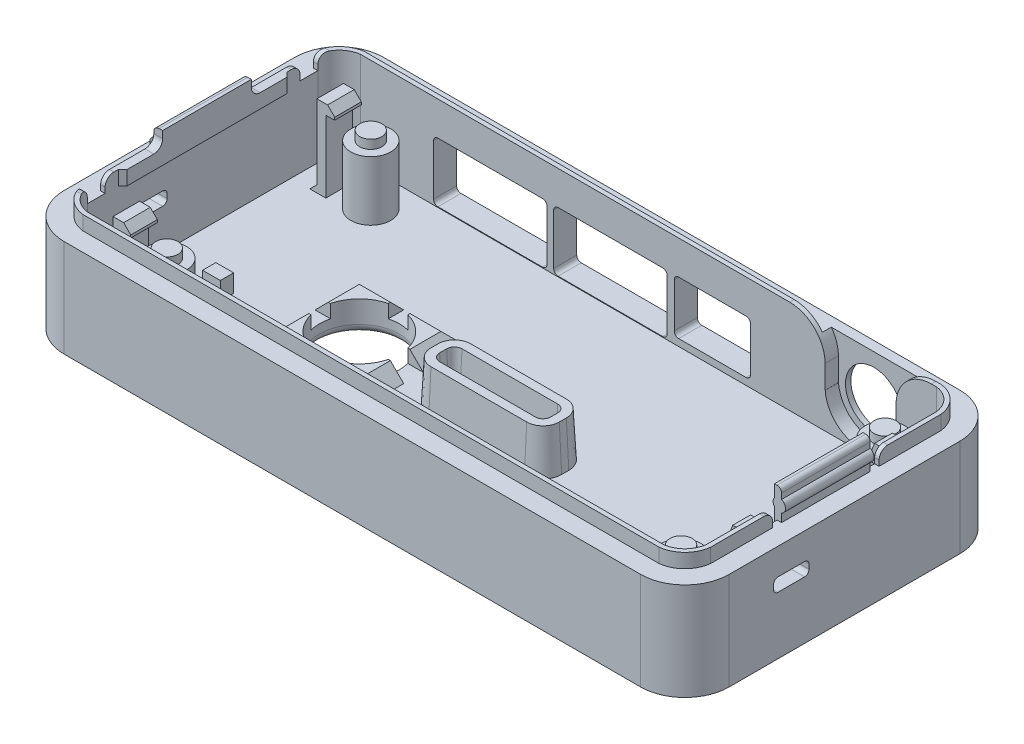
SolidWorks part; units mm, degrees
ref_plane "前视基准面" through (0, 0, 0) normal (0, 0, 1) x (1, 0, 0)
ref_plane "上视基准面" through (0, 0, 0) normal (0, 1, 0) x (1, 0, 0)
ref_plane "右视基准面" through (0, 0, 0) normal (1, 0, 0) x (0, 0, -1)
sketch "zero" plane through (0, 0, 0) normal (0, 1, 0) x (1, 0, 0)
  line L1 (-29.5, 15) -> (29.5, 15)
  line L2 (-32.5, 12) -> (-32.5, -12)
  line L3 (-29.5, -15) -> (29.5, -15)
  line L4 (32.5, 12) -> (32.5, -12)
  line L5 (-32.5, 15) -> (32.5, -15) construction
  line L6 (-32.5, -15) -> (32.5, 15) construction
  line L7 (-25.7, -15) -> (-14.5, -15)
  line L8 (-25.7, -15) -> (-25.7, -9.6569)
  line L9 (-25.7, -9.6569) -> (-14.5, -9.6569)
  line L10 (-14.5, -15) -> (-14.5, -9.6569)
  line L11 (5.2, -15) -> (12.7, -15)
  line L12 (5.2, -15) -> (5.2, -11)
  line L13 (5.2, -11) -> (12.7, -11)
  line L14 (12.7, -15) -> (12.7, -11)
  line L15 (17.8, -15) -> (25.3, -15)
  line L16 (17.8, -15) -> (17.8, -11)
  line L17 (17.8, -11) -> (25.3, -11)
  line L18 (25.3, -15) -> (25.3, -11)
  line L19 (-32.5, 7.7) -> (-19.5, 7.7)
  line L20 (-32.5, 7.7) -> (-32.5, -4.3)
  line L21 (-32.5, -4.3) -> (-19.5, -4.3)
  line L22 (-19.5, 7.7) -> (-19.5, -4.3)
  line L23 (-25.5, 14) -> (25.5, 14)
  line L24 (-25.5, 14) -> (-25.5, 8.8)
  line L25 (-25.5, 8.8) -> (25.5, 8.8)
  line L26 (25.5, 14) -> (25.5, 8.8)
  line L27 (-19.5, 7.2329) -> (-35.5, 7.2329)
  line L28 (-19.5, 7.2329) -> (-19.5, -3.7671)
  line L29 (-19.5, -3.7671) -> (-35.5, -3.7671)
  line L30 (-35.5, 7.2329) -> (-35.5, -3.7671)
  arc A0 (29.5, -15) -> (32.5, -12) centre (29.5, -12) ccw
  arc A1 (29.5, 15) -> (32.5, 12) centre (29.5, 12) cw
  arc A2 (-32.5, -12) -> (-29.5, -15) centre (-29.5, -12) ccw
  arc A3 (-29.5, 15) -> (-32.5, 12) centre (-29.5, 12) ccw
  circle A4 centre (-29, 11.4) radius 3
  circle A5 centre (-29, -11.5) radius 3
  circle A6 centre (29, 11.4) radius 3
  circle A7 centre (29, -11.5) radius 3
  circle A8 centre (-29, 11.4) radius 1.375
  circle A9 centre (-29, -11.5) radius 1.375
  circle A10 centre (29, -11.5) radius 1.375
  circle A11 centre (29, 11.4) radius 1.375
  point P0 (0, 0)
  dimension "D3" = 3
  dimension "D4" = 6
  dimension "D9" = 2.75
  dimension "D1" = 65
  dimension "D2" = 30
  dimension "D5" = 3.6
  dimension "D6" = 3.5
  dimension "D7" = 3.5
  dimension "D8" = 3.5
  dimension "D10" = 12
  dimension "D11" = 7.3
  dimension "D12" = 13
  dimension "D13" = 11.2
  dimension "D14" = 6.8
  dimension "D15" = 19.7
  dimension "D16" = 7.5
  dimension "D17" = 7.5
  dimension "D18" = 5.1
  dimension "D19" = 4
  dimension "D20" = 5.2
  dimension "D21" = 7
  dimension "D22" = 7
  dimension "D23" = 1
  dimension "D24" = 11
  dimension "D25" = 16
sketch "sugar" plane through (0, 0, 0) normal (0, 1, 0) x (1, 0, 0)
  line L1 (-29.5, 15) -> (29.5, 15)
  line L2 (-32.5, 12) -> (-32.5, -12)
  line L3 (-29.5, -15) -> (29.5, -15)
  line L4 (32.5, 12) -> (32.5, -12)
  line L5 (-32.5, 15) -> (32.5, -15) construction
  line L6 (-32.5, -15) -> (32.5, 15) construction
  line L7 (23.5, -11.5) -> (19.5, -11.5)
  line L8 (23.5, -11.5) -> (23.5, -13.9082)
  line L9 (23.5, -13.9082) -> (19.5, -13.9082)
  line L10 (19.5, -11.5) -> (19.5, -13.9082)
  line L11 (16, -11.0071) -> (8.5, -11.0071)
  line L12 (16, -11.0071) -> (16, -15)
  line L13 (16, -15) -> (8.5, -15)
  line L14 (8.5, -11.0071) -> (8.5, -15)
  line L15 (20.5, -13.9082) -> (22.5, -13.9082)
  line L16 (20.5, -13.9082) -> (20.5, -14.8173)
  line L17 (20.5, -14.8173) -> (22.5, -14.8173)
  line L18 (22.5, -13.9082) -> (22.5, -14.8173)
  arc A0 (29.5, 15) -> (32.5, 12) centre (29.5, 12) cw
  arc A1 (29.5, -15) -> (32.5, -12) centre (29.5, -12) ccw
  arc A2 (-32.5, -12) -> (-29.5, -15) centre (-29.5, -12) ccw
  arc A3 (-29.5, 15) -> (-32.5, 12) centre (-29.5, 12) ccw
  circle A4 centre (-29, 11.4) radius 3
  circle A5 centre (-29, 11.4) radius 1.375
  circle A6 centre (-29, -11.5) radius 3
  circle A7 centre (-29, -11.5) radius 1.375
  circle A8 centre (29, 11.4) radius 3
  circle A9 centre (29, 11.4) radius 1.375
  circle A10 centre (29, -11.5) radius 3
  circle A11 centre (29, -11.5) radius 1.375
  dimension "D3" = 3
  dimension "D1" = 65
  dimension "D2" = 30
  dimension "D4" = 9
  dimension "D5" = 4
  dimension "D6" = 3.5
  dimension "D7" = 7.5
  dimension "D8" = 2
  dimension "D9" = 1
sketch "case" plane through (0, 0, 0) normal (0, 1, 0) x (1, 0, 0)
  line L1 (-34.0422, 18) -> (30.9578, 18)
  line L2 (-39.0422, 13) -> (-39.0422, -13)
  line L3 (-34.0422, -18) -> (30.9578, -18)
  line L4 (35.9578, 13) -> (35.9578, -13)
  line L5 (-39.0422, 18) -> (35.9578, -18) construction
  line L6 (-39.0422, -18) -> (35.9578, 18) construction
  arc A0 (-39.0422, -13) -> (-34.0422, -18) centre (-34.0422, -13) ccw
  arc A1 (30.9578, -18) -> (35.9578, -13) centre (30.9578, -13) ccw
  arc A2 (30.9578, 18) -> (35.9578, 13) centre (30.9578, 13) cw
  arc A3 (-34.0422, 18) -> (-39.0422, 13) centre (-34.0422, 13) ccw
  point P0 (-1.5422, 0)
  point P3 (-1.5422, 0)
  dimension "D3" = 5
  dimension "D1" = 75
  dimension "D2" = 36
extrude "凸台-拉伸2" add sketch "case" along normal blind 11
sketch "草图2" plane through (0, 0, 0) normal (0, 1, 0) x (1, 0, 0)
  line L4 (-34.0422, -15.4) -> (30.9578, -15.4)
  line L5 (33.3578, -13) -> (33.3578, 13)
  line L6 (30.9578, 15.4) -> (-34.0422, 15.4)
  line L7 (-36.4422, 13) -> (-36.4422, -13)
  line L12 (33.8578, -13) -> (33.8578, 13)
  line L13 (30.9578, 15.9) -> (-34.0422, 15.9)
  line L14 (-36.9422, 13) -> (-36.9422, -13)
  line L15 (-34.0422, -15.9) -> (30.9578, -15.9)
  arc A4 (30.9578, -15.4) -> (33.3578, -13) centre (30.583, -12.6252) ccw
  arc A5 (33.3578, 13) -> (30.9578, 15.4) centre (30.583, 12.6252) ccw
  arc A6 (-34.0422, 15.4) -> (-36.4422, 13) centre (-33.6674, 12.6252) ccw
  arc A7 (-36.4422, -13) -> (-34.0422, -15.4) centre (-33.6674, -12.6252) ccw
  arc A12 (30.9578, -15.9) -> (33.8578, -13) centre (30.5796, -12.6217) ccw
  arc A13 (33.8578, 13) -> (30.9578, 15.9) centre (30.5796, 12.6217) ccw
  arc A14 (-34.0422, 15.9) -> (-36.9422, 13) centre (-33.6639, 12.6217) ccw
  arc A15 (-36.9422, -13) -> (-34.0422, -15.9) centre (-33.6639, -12.6217) ccw
  point P13 (0, 0)
  point P14 (0, 0)
  point P15 (0, 0)
ref_plane "基准面1" through (0, 11, 0) normal (0, 1, 0) x (1, 0, 0)
sketch "草图3" plane through (0, 11, 0) normal (0, 1, 0) x (1, 0, 0)
  line L4 (-34.0422, -15.4) -> (30.9578, -15.4)
  line L5 (33.3578, -13) -> (33.3578, 13)
  line L6 (30.9578, 15.4) -> (-34.0422, 15.4)
  line L7 (-36.4422, 13) -> (-36.4422, -13)
  line L8 (-34.0422, -15.4) -> (30.9578, -15.4)
  line L9 (33.3578, -13) -> (33.3578, 13)
  line L10 (30.9578, 15.4) -> (-34.0422, 15.4)
  line L11 (-36.4422, 13) -> (-36.4422, -13)
  line L12 (-36.9422, 13) -> (-36.9422, -13)
  line L13 (-34.0422, -15.9) -> (30.9578, -15.9)
  line L14 (33.8578, -13) -> (33.8578, 13)
  line L15 (30.9578, 15.9) -> (-34.0422, 15.9)
  line L16 (-36.9422, 13) -> (-36.9422, -13)
  line L17 (-34.0422, -15.9) -> (30.9578, -15.9)
  line L18 (33.8578, -13) -> (33.8578, 13)
  line L19 (30.9578, 15.9) -> (-34.0422, 15.9)
  arc A4 (30.9578, -15.4) -> (33.3578, -13) centre (30.583, -12.6252) ccw
  arc A5 (33.3578, 13) -> (30.9578, 15.4) centre (30.583, 12.6252) ccw
  arc A6 (-34.0422, 15.4) -> (-36.4422, 13) centre (-33.6674, 12.6252) ccw
  arc A7 (-36.4422, -13) -> (-34.0422, -15.4) centre (-33.6674, -12.6252) ccw
  arc A8 (30.9578, -15.4) -> (33.3578, -13) centre (30.583, -12.6252) ccw
  arc A9 (33.3578, 13) -> (30.9578, 15.4) centre (30.583, 12.6252) ccw
  arc A10 (-34.0422, 15.4) -> (-36.4422, 13) centre (-33.6674, 12.6252) ccw
  arc A11 (-36.4422, -13) -> (-34.0422, -15.4) centre (-33.6674, -12.6252) ccw
  arc A12 (-36.9422, -13) -> (-34.0422, -15.9) centre (-33.6639, -12.6217) ccw
  arc A13 (30.9578, -15.9) -> (33.8578, -13) centre (30.5796, -12.6217) ccw
  arc A14 (33.8578, 13) -> (30.9578, 15.9) centre (30.5796, 12.6217) ccw
  arc A15 (-34.0422, 15.9) -> (-36.9422, 13) centre (-33.6639, 12.6217) ccw
  arc A16 (-36.9422, -13) -> (-34.0422, -15.9) centre (-33.6639, -12.6217) ccw
  arc A17 (30.9578, -15.9) -> (33.8578, -13) centre (30.5796, -12.6217) ccw
  arc A18 (33.8578, 13) -> (30.9578, 15.9) centre (30.5796, 12.6217) ccw
  arc A19 (-34.0422, 15.9) -> (-36.9422, 13) centre (-33.6639, 12.6217) ccw
  dimension "D1" = 0
  dimension "D2" = 0
extrude "凸台-拉伸4" add sketch "草图3" along normal blind 1.6
sketch "草图5" plane through (0, 11, 0) normal (0, 1, 0) x (1, 0, 0)
  line L0 (33.3578, -13) -> (33.3578, 13) construction
  line L1 (33.0578, 5) -> (33.3578, 5)
  line L2 (33.0578, 5) -> (33.0578, -5)
  line L3 (33.0578, -5) -> (33.3578, -5)
  line L4 (33.3578, 5) -> (33.3578, -5)
  line L5 (33.0578, 5) -> (33.3578, -5) construction
  line L6 (33.0578, -5) -> (33.3578, 5) construction
  point P0 (33.2078, 0)
  dimension "D2" = 10
  dimension "D3" = 0.3
  dimension "D4" = 0
ref_plane "基准面3" through (33.8578, 0, 0) normal (1, 0, 0) x (0, 0, -1)
ref_plane "基准面7" through (-36.9422, 0, 0) normal (-1, 0, 0) x (0, 0, 1)
ref_plane "基准面8" through (0, 0, 0) normal (0, -1, 0) x (-1, 0, 0)
sketch "草图14" plane through (0, 11, 0) normal (0, 1, 0) x (1, 0, 0)
  line L4 (-34.0422, -15.4) -> (30.9578, -15.4)
  line L5 (33.3578, -13) -> (33.3578, 13)
  line L6 (30.9578, 15.4) -> (-34.0422, 15.4)
  line L7 (-36.4422, 13) -> (-36.4422, -13)
  line L8 (-34.0422, -15.4) -> (30.9578, -15.4)
  line L9 (33.3578, -13) -> (33.3578, 13)
  line L10 (30.9578, 15.4) -> (-34.0422, 15.4)
  line L11 (-36.4422, 13) -> (-36.4422, -13)
  arc A4 (30.9578, -15.4) -> (33.3578, -13) centre (30.583, -12.6252) ccw
  arc A5 (33.3578, 13) -> (30.9578, 15.4) centre (30.583, 12.6252) ccw
  arc A6 (-34.0422, 15.4) -> (-36.4422, 13) centre (-33.6674, 12.6252) ccw
  arc A7 (-36.4422, -13) -> (-34.0422, -15.4) centre (-33.6674, -12.6252) ccw
  arc A8 (30.9578, -15.4) -> (33.3578, -13) centre (30.583, -12.6252) ccw
  arc A9 (33.3578, 13) -> (30.9578, 15.4) centre (30.583, 12.6252) ccw
  arc A10 (-34.0422, 15.4) -> (-36.4422, 13) centre (-33.6674, 12.6252) ccw
  arc A11 (-36.4422, -13) -> (-34.0422, -15.4) centre (-33.6674, -12.6252) ccw
  dimension "D1" = 0
extrude "切除-拉伸2" cut sketch "草图14" against normal blind 9
extrude "凸台-拉伸12" add sketch "草图5" against normal blind 2 and the other way blind 1.6
sketch "草图15" plane through (0, 2, 0) normal (0, 1, 0) x (1, 0, 0)
  line L1 (35.9578, -13) -> (35.9578, 13) construction
  line L5 (-39.0422, 13) -> (-39.0422, -13) construction
  line L6 (-34.0422, -18) -> (30.9578, -18) construction
  line L7 (30.9578, 18) -> (-34.0422, 18) construction
  circle A0 centre (29.0603, -11.5295) radius 2.25
  circle A1 centre (-28.9397, -11.5295) radius 2.25
  circle A2 centre (29.0603, 11.4705) radius 2.25
  circle A3 centre (-28.9397, 11.4705) radius 2.25
  dimension "D1" = 4.5
  dimension "D2" = 6.8975
  dimension "D3" = 10.1025
  dimension "D4" = 6.4705
  dimension "D5" = 6.5295
extrude "凸台-拉伸13" add sketch "草图15" along normal blind 6.7
sketch "草图16" plane through (0, 8.7, 0) normal (0, 1, 0) x (1, 0, 0)
  circle A0 centre (29.0603, -11.5295) radius 1.25
  circle A1 centre (29.0603, 11.4705) radius 1.25
  circle A2 centre (-28.9397, -11.5295) radius 1.25
  circle A3 centre (-28.9397, 11.4705) radius 1.25
  dimension "D1" = 2.5
extrude "凸台-拉伸14" add sketch "草图16" along normal blind 1
sketch "草图17" plane through (0, 12.6, 0) normal (0, 1, 0) x (1, 0, 0)
  line L0 (33.3578, -13) -> (33.3578, -5) construction
  line L1 (33.3578, -5) -> (33.8578, -5)
  line L2 (33.3578, -5) -> (33.3578, -6)
  line L3 (33.3578, -6) -> (33.8578, -6)
  line L4 (33.8578, -5) -> (33.8578, -6)
  line L5 (33.3578, -13) -> (33.3578, 13) construction
  line L6 (33.8578, -13) -> (33.8578, 13) construction
  line L8 (33.3578, 5) -> (33.8578, 5)
  line L9 (33.3578, 5) -> (33.3578, 6)
  line L10 (33.3578, 6) -> (33.8578, 6)
  line L11 (33.8578, 5) -> (33.8578, 6)
  dimension "D1" = 1
  dimension "D2" = 1
extrude "切除-拉伸3" cut sketch "草图17" against normal blind 1.6
sketch "草图19" plane through (0, 12.6, 0) normal (0, 1, 0) x (1, 0, 0)
  line L0 (33.0578, 5) -> (33.0578, -5) construction
  line L1 (33.8578, -5) -> (33.0578, -5)
  line L2 (33.8578, -5) -> (33.8578, 5)
  line L3 (33.8578, 5) -> (33.0578, 5)
  line L4 (33.0578, -5) -> (33.0578, 5)
extrude "凸台-拉伸15" add sketch "草图19" along normal blind 1.8
sketch "草图20" plane through (0, 0, -5) normal (0, 0, -1) x (-1, 0, 0)
  line L0 (-30.9578, 11) -> (-35.9578, 11) construction
  line L3 (-33.8578, 11) -> (-33.8578, 14.4) construction
  circle A0 centre (-33.6078, 12.6) radius 0.7
  dimension "D1" = 1.4
  dimension "D2" = 1.6
  dimension "D3" = 0.25
extrude "凸台-拉伸16" add sketch "草图20" against normal blind 10
fillet "圆角4" radius 0.5 1 edges at (33.8578, 14.4, 0)
sketch "草图39" plane through (0, 0, -18) normal (0, 0, -1) x (-1, 0, 0)
  line L0 (-30.9578, 0) -> (34.0422, 0) construction
  line L1 (-35.9578, 11) -> (-35.9578, 0) construction
  circle A0 centre (-22.3721, 6.2789) radius 4
  dimension "D1" = 6.2789
  dimension "D3" = 8
  dimension "D2" = 13.5857
extrude "切除-拉伸4" cut sketch "草图39" against normal blind 0.5
sketch "草图41" plane through (0, 0, -18) normal (0, 0, -1) x (-1, 0, 0)
  line L0 (-30.9578, 0) -> (34.0422, 0) construction
  line L1 (-9.9578, 2.7789) -> (-1.3578, 2.7789)
  line L2 (-9.9578, 2.7789) -> (-9.9578, 8.7789)
  line L3 (-9.9578, 8.7789) -> (-1.3578, 8.7789)
  line L4 (-1.3578, 2.7789) -> (-1.3578, 8.7789)
  line L5 (-0.5578, 2.0789) -> (12.2422, 2.0789)
  line L6 (-0.5578, 2.0789) -> (-0.5578, 8.7789)
  line L7 (-0.5578, 8.7789) -> (12.2422, 8.7789)
  line L8 (12.2422, 2.0789) -> (12.2422, 8.7789)
  line L9 (12.9922, 2.0789) -> (25.7922, 2.0789)
  line L10 (12.9922, 2.0789) -> (12.9922, 8.7789)
  line L11 (12.9922, 8.7789) -> (25.7922, 8.7789)
  line L12 (25.7922, 2.0789) -> (25.7922, 8.7789)
  line L13 (-35.9578, 11) -> (-35.9578, 0) construction
  dimension "D1" = 8.7789
  dimension "D2" = 26
  dimension "D3" = 8.6
  dimension "D4" = 6
  dimension "D5" = 0.8
  dimension "D6" = 6.7
  dimension "D7" = 12.8
  dimension "D8" = 0.75
  dimension "D9" = 12.8
extrude "切除-拉伸5" cut sketch "草图41" against normal blind 12
sketch "草图42" plane through (0, 0, -17.5) normal (0, 0, -1) x (-1, 0, 0)
  circle A0 centre (-22.3721, 6.2789) radius 3.2
  circle A1 centre (-22.3721, 6.2789) radius 4 construction
extrude "切除-拉伸6" cut sketch "草图42" against normal blind 1.6
sketch "草图46" plane through (-36.4422, 0, 0) normal (1, 0, 0) x (0, 0, -1)
  line L0 (13, 12.6) -> (-13, 12.6) construction
  line L1 (-10, 12.6) -> (10, 12.6)
  line L2 (-10, 12.6) -> (-10, 11)
  line L3 (-10, 11) -> (10, 11)
  line L4 (10, 12.6) -> (10, 11)
  line L6 (-18, 11) -> (-18, 0) construction
  dimension "D1" = 8
  dimension "D2" = 8
extrude "凸台-拉伸19" add sketch "草图46" along normal blind 0.5
chamfer "倒角3" distance 1 angle 45 2 edges at (-35.9422, 11.8, -10) (-35.9422, 11.8, 10)
sketch "草图48" plane through (0, 12.6, 0) normal (0, 1, 0) x (1, 0, 0)
  line L0 (-35.9422, 9) -> (-35.9422, -9) construction
  line L1 (-35.9422, -5) -> (-36.9422, -5)
  line L2 (-35.9422, -5) -> (-35.9422, 5)
  line L3 (-35.9422, 5) -> (-36.9422, 5)
  line L4 (-36.9422, -5) -> (-36.9422, 5)
  line L5 (-36.9422, 13) -> (-36.9422, -13) construction
extrude "凸台-拉伸21" add sketch "草图48" along normal blind 1.8
sketch "草图49" plane through (0, 0, 5) normal (0, 0, 1) x (1, 0, 0)
  line L0 (-34.0422, 11) -> (-39.0422, 11) construction
  line L1 (-36.9422, 14.4) -> (-36.9422, 12.6) construction
  circle A0 centre (-36.6922, 12.6) radius 0.7
  dimension "D1" = 1.4
  dimension "D2" = 1.6
  dimension "D3" = 0.25
extrude "凸台-拉伸22" add sketch "草图49" against normal blind 10
sketch "草图50" plane through (0, 12.6, 0) normal (0, 1, 0) x (1, 0, 0)
  line L0 (-36.4422, 13) -> (-36.4422, 9.5) construction
  line L1 (-36.4422, 13) -> (-36.9422, 13)
  line L2 (-36.4422, 13) -> (-36.4422, 11)
  line L3 (-36.4422, 11) -> (-36.9422, 11)
  line L4 (-36.9422, 13) -> (-36.9422, 11)
  line L5 (-36.9422, 13) -> (-36.9422, 5) construction
  line L6 (-36.4422, -9.5) -> (-36.4422, -13) construction
  line L7 (-36.4422, -11) -> (-36.9422, -11)
  line L8 (-36.4422, -11) -> (-36.4422, -13)
  line L9 (-36.4422, -13) -> (-36.9422, -13)
  line L10 (-36.9422, -11) -> (-36.9422, -13)
  line L11 (-36.9422, -5) -> (-36.9422, -13) construction
  line L12 (30.9578, 18) -> (-34.0422, 18) construction
  line L13 (-34.0422, -18) -> (30.9578, -18) construction
  dimension "D1" = 2
  dimension "D2" = 2
  dimension "D3" = 5
  dimension "D4" = 5
extrude "切除-拉伸10" cut sketch "草图50" against normal blind 1.6
fillet "圆角9" radius 1 6 edges at (33.6078, 12.6, 6) (33.6078, 12.6, -6) (-36.6922, 12.6, -13) (-36.6922, 12.6, -11) (-36.6922, 12.6, 11) (-36.6922, 12.6, 13)
fillet "圆角10" radius 0.6 1 edges at (-36.9422, 14.4, 0)
sketch "草图51" plane through (0, 0, 0) normal (0, -1, 0) x (1, 0, 0)
  line L0 (35.9578, 13) -> (35.9578, -13) construction
  line L1 (6.2578, 2.3) -> (-5.7422, 2.3)
  line L2 (6.2578, 2.3) -> (6.2578, 4.3)
  line L3 (6.2578, 4.3) -> (-5.7422, 4.3)
  line L4 (-5.7422, 2.3) -> (-5.7422, 4.3)
  line L5 (30.9578, -18) -> (-34.0422, -18) construction
  dimension "D1" = 2
  dimension "D2" = 12
  dimension "D3" = 29.7
  dimension "D4" = 20.3
extrude "切除-拉伸11" cut sketch "草图51" against normal blind 2
fillet "圆角13" radius 0.6 4 edges at (-5.7422, 1, 4.3) (-5.7422, 1, 2.3) (6.2578, 1, 4.3) (6.2578, 1, 2.3)
sketch "草图52" plane through (0, 2, 0) normal (0, 1, 0) x (1, 0, 0)
  line L0 (-11.5279, -7.2295) -> (-20.7279, -7.2295)
  line L5 (-20.7279, -7.2295) -> (-20.7279, 1.9705)
  line L6 (-11.5279, 1.9705) -> (-20.7279, 1.9705)
  line L7 (-11.5279, -7.2295) -> (-11.5279, 1.9705)
  line L8 (-39.0422, 13) -> (-39.0422, -13) construction
  line L9 (-34.0422, -18) -> (30.9578, -18) construction
  dimension "D1" = 9.2
  dimension "D2" = 9.2
  dimension "D3" = 18.3143
  dimension "D4" = 10.7705
extrude "凸台-拉伸23" add sketch "草图52" along normal blind 1.5
chamfer "倒角5" distance 1.5 angle 45 4 edges at (-16.1279, 2, -1.9705) (-11.5279, 2, 2.6295) (-16.1279, 2, 7.2295) (-20.7279, 2, 2.6295)
sketch "草图53" plane through (0, 0, 0) normal (0, -1, 0) x (1, 0, 0)
  line L1 (30.9578, -18) -> (-34.0422, -18) construction
  line L2 (-39.0422, -13) -> (-39.0422, 13) construction
  circle A0 centre (-16.1279, 2.6295) radius 4.5
  dimension "D1" = 9
  dimension "D2" = 20.6295
  dimension "D3" = 22.9143
extrude "切除-拉伸12" cut sketch "草图53" against normal up to next
fillet "圆角14" radius 1 1 edges at (-16.1279, 0, -1.8705)
sketch "草图55" plane through (0, 3.5, 0) normal (0, 1, 0) x (1, 0, 0)
  line L1 (-10.0279, -3.7295) -> (-22.2279, -3.7295)
  line L2 (-10.0279, -3.7295) -> (-10.0279, -1.5295)
  line L3 (-10.0279, -1.5295) -> (-22.2279, -1.5295)
  line L4 (-22.2279, -3.7295) -> (-22.2279, -1.5295)
  line L5 (-10.0279, -3.7295) -> (-22.2279, -1.5295) construction
  line L6 (-10.0279, -1.5295) -> (-22.2279, -3.7295) construction
  circle A0 centre (-16.1279, -2.6295) radius 4.5 construction
  point P0 (-16.1279, -2.6295)
  dimension "D1" = 12.2
  dimension "D2" = 2.2
extrude "切除-拉伸13" cut sketch "草图55" against normal blind 1.5
sketch "草图56" plane through (0, 3.5, 0) normal (0, 1, 0) x (1, 0, 0)
  line L1 (-15.0279, -8.7295) -> (-17.2279, -8.7295)
  line L2 (-15.0279, -8.7295) -> (-15.0279, 3.4705)
  line L3 (-15.0279, 3.4705) -> (-17.2279, 3.4705)
  line L4 (-17.2279, -8.7295) -> (-17.2279, 3.4705)
  line L5 (-15.0279, -8.7295) -> (-17.2279, 3.4705) construction
  line L6 (-15.0279, 3.4705) -> (-17.2279, -8.7295) construction
  arc A0 (-11.7644, -3.7295) -> (-11.7644, -1.5295) centre (-16.1279, -2.6295) ccw construction
  point P0 (-16.1279, -2.6295)
  dimension "D1" = 12.2
  dimension "D2" = 2.2
extrude "切除-拉伸14" cut sketch "草图56" against normal blind 1.5
sketch "草图62" plane through (0, 0, 0) normal (0, -1, 0) x (1, 0, 0)
  line L54 (31.3299, 13.3324) -> (30.9169, 13.5642)
  line L55 (30.9169, 13.5642) -> (28.7745, 14.7678)
  line L56 (28.7745, 14.7678) -> (28.3615, 15.0024)
  line L57 (27.5011, 14.9926) -> (27.0935, 14.7486)
  line L58 (27.0935, 14.7486) -> (24.9793, 13.4962)
  line L60 (24.9793, 13.4962) -> (24.5717, 13.255)
  line L61 (24.15, 12.5065) -> (24.189, 9.0989)
  line L62 (24.6278, 8.3602) -> (25.0408, 8.1284)
  line L63 (25.0408, 8.1284) -> (27.1831, 6.9248)
  line L65 (27.1831, 6.9248) -> (27.5962, 6.6902)
  line L66 (28.4566, 6.7) -> (28.8641, 6.9441)
  line L67 (28.8641, 6.9441) -> (30.9784, 8.1964)
  line L68 (30.9784, 8.1964) -> (31.3859, 8.4376)
  line L69 (31.8076, 9.1861) -> (31.7686, 12.5937)
  line L70 (25.1226, 12.9222) -> (27.7378, 14.4738)
  line L73 (28.1396, 14.4784) -> (30.7754, 12.9841)
  line L74 (30.7822, 12.6337) -> (28.2554, 11.0831)
  line L75 (29.0741, 8.5137) -> (28.7797, 8.3451)
  line L76 (28.7517, 8.2963) -> (28.7615, 7.4416)
  line L77 (28.7336, 7.3928) -> (28.1845, 7.0731)
  line L78 (28.1013, 7.1205) -> (28.0711, 9.7589)
  line L79 (28.099, 9.8076) -> (29.0331, 10.3512)
  line L80 (31.0237, 8.7127) -> (30.4803, 8.3959)
  line L81 (30.3971, 8.4434) -> (30.3827, 9.6998)
  line L82 (30.4107, 9.7486) -> (30.9541, 10.0626)
  line L83 (31.0373, 10.0151) -> (31.0517, 8.7615)
  line L84 (29.0341, 9.0205) -> (28.7735, 8.8864)
  line L85 (28.7443, 8.9459) -> (28.7366, 9.6183)
  line L86 (28.7646, 9.6671) -> (29.008, 9.8066)
  line L129 (28.7735, 8.8864) -> (28.7797, 8.3451)
  line L130 (28.7443, 8.9459) -> (28.7517, 8.2963)
  spline S0 degree 3 poles (28.3615, 15.0024) (28.2268, 15.075) (28.0782, 15.1132) (27.93, 15.1115) knots 3 3 3 3 4 4 4 4
  spline S1 degree 3 poles (27.93, 15.1115) (27.7818, 15.1098) (27.6341, 15.0682) (27.5011, 14.9926) knots 4 4 4 4 5 5 5 5
  spline S2 degree 3 poles (24.5717, 13.255) (24.3085, 13.0981) (24.1465, 12.8113) (24.15, 12.5065) knots 8 8 8 8 9 9 9 9
  spline S3 degree 3 poles (24.189, 9.0989) (24.1926, 8.7912) (24.3611, 8.511) (24.6278, 8.3602) knots 10 10 10 10 11 11 11 11
  spline S4 degree 3 poles (27.5962, 6.6902) (27.7309, 6.6148) (27.8795, 6.5794) (28.0277, 6.5811) knots 14 14 14 14 15 15 15 15
  spline S5 degree 3 poles (28.0277, 6.5811) (28.1759, 6.5828) (28.3236, 6.6216) (28.4566, 6.7) knots 15 15 15 15 16 16 16 16
  spline S6 degree 3 poles (31.3859, 8.4376) (31.652, 8.5945) (31.8112, 8.8784) (31.8076, 9.1861) knots 19 19 19 19 20 20 20 20
  spline S7 degree 3 poles (31.7686, 12.5937) (31.7651, 12.8986) (31.5995, 13.1816) (31.3299, 13.3324) knots 21 21 21 21 22 22 22 22
  spline S8 degree 2 poles (27.6998, 11.0768) (25.1072, 12.5345) (25.1014, 12.5373) knots 0 0 0 1 1 1
  spline S9 degree 3 poles (25.1014, 12.5373) (24.9664, 12.6326) (24.9783, 12.838) (25.1226, 12.9222) knots 1 1 1 1 2 2 2 2
  spline S10 degree 3 poles (27.7378, 14.4738) (27.8595, 14.5465) (28.0134, 14.5482) (28.1396, 14.4784) knots 3 3 3 3 4 4 4 4
  spline S11 degree 3 poles (30.7754, 12.9841) (30.9101, 12.9087) (30.9152, 12.715) (30.7822, 12.6337) knots 5 5 5 5 6 6 6 6
  spline S12 degree 3 poles (28.2554, 11.0831) (28.0856, 10.9815) (27.8719, 10.979) (27.6998, 11.0768) knots 7 7 7 7 8 8 8 8
  spline S13 degree 3 poles (28.7615, 7.4416) (28.7618, 7.4216) (28.7534, 7.4044) (28.7336, 7.3928) knots 3 3 3 3 4 4 4 4
  spline S14 degree 3 poles (28.1845, 7.0731) (28.1477, 7.0527) (28.1018, 7.0778) (28.1013, 7.1205) knots 5 5 5 5 6 6 6 6
  spline S15 degree 3 poles (28.0711, 9.7589) (28.0708, 9.7788) (28.0792, 9.7988) (28.099, 9.8076) knots 7 7 7 7 8 8 8 8
  spline S16 degree 3 poles (29.0331, 10.3512) (29.6389, 10.7029) (30.1424, 10.7771) (30.1502, 10.0933) knots 9 9 9 9 10 10 10 10
  spline S17 degree 3 poles (30.1502, 10.0933) (30.1577, 9.4351) (29.6544, 8.8509) (29.0741, 8.5137) knots 10 10 10 10 11 11 11 11
  spline S18 degree 3 poles (31.0517, 8.7615) (31.0519, 8.7415) (31.0407, 8.7214) (31.0237, 8.7127) knots 0 0 0 0 1 1 1 1
  spline S19 degree 3 poles (30.4803, 8.3959) (30.4435, 8.3755) (30.3976, 8.4006) (30.3971, 8.4434) knots 2 2 2 2 3 3 3 3
  spline S20 degree 3 poles (30.3827, 9.6998) (30.3825, 9.7198) (30.3937, 9.737) (30.4107, 9.7486) knots 4 4 4 4 5 5 5 5
  spline S21 degree 3 poles (30.9541, 10.0626) (30.991, 10.0829) (31.0368, 10.0578) (31.0373, 10.0151) knots 6 6 6 6 7 7 7 7
  spline S22 degree 3 poles (30.6996, 10.8946) (30.9175, 11.0224) (31.0748, 10.9701) (31.0771, 10.7707) (31.0794, 10.5741) (30.9253, 10.3415) (30.7073, 10.2165) knots 2 2 2 2 3 3 3 4 4 4 4
  spline S23 degree 3 poles (30.7073, 10.2165) (30.4866, 10.0857) (30.3293, 10.1381) (30.327, 10.3346) (30.3247, 10.5369) (30.4788, 10.7667) (30.6996, 10.8946) knots 0 0 0 0 1 1 1 2 2 2 2
  spline S24 degree 3 poles (29.5048, 9.7183) (29.5079, 9.4476) (29.3569, 9.2065) (29.0341, 9.0205) knots 0 0 0 0 1 1 1 1
  spline S25 degree 3 poles (28.7366, 9.6183) (28.7364, 9.6382) (28.7475, 9.6583) (28.7646, 9.6671) knots 4 4 4 4 5 5 5 5
  spline S26 degree 3 poles (29.008, 9.8066) (29.325, 9.9926) (29.5016, 9.9975) (29.5048, 9.7183) knots 6 6 6 6 7 7 7 7
fillet "圆角17" radius 1 2 edges at (-36.4422, 12.6, 5) (-36.4422, 12.6, -5)
sketch "草图63" plane through (0, 2, 0) normal (0, 1, 0) x (1, 0, 0)
  line L0 (30.9578, 15.4) -> (-34.0422, 15.4) construction
  line L1 (-30.4422, -4.5) -> (-28.4422, -4.5)
  line L2 (-30.4422, -4.5) -> (-30.4422, -6)
  line L3 (-30.4422, -6) -> (-28.4422, -6)
  line L4 (-28.4422, -4.5) -> (-28.4422, -6)
  line L5 (-36.4422, 13) -> (-36.4422, -13) construction
  dimension "D1" = 2
  dimension "D2" = 1.5
  dimension "D3" = 19.9
  dimension "D4" = 6
extrude "凸台-拉伸24" add sketch "草图63" along normal blind 2
fillet "圆角18" radius 0.5 12 edges at (1.3578, 8.7789, -16.7) (9.9578, 8.7789, -16.7) (9.9578, 2.7789, -16.7) (1.3578, 2.7789, -16.7) (-12.2422, 2.0789, -16.7) (0.5578, 2.0789, -16.7) (0.5578, 8.7789, -16.7) (-12.2422, 8.7789, -16.7) (-25.7922, 8.7789, -16.7) (-12.9922, 8.7789, -16.7) (-25.7922, 2.0789, -16.7) (-12.9922, 2.0789, -16.7)
sketch "草图66" plane through (0, 2, 0) normal (0, 1, 0) x (1, 0, 0)
  line L8 (-5.1422, -0.8) -> (5.6578, -0.8)
  line L9 (-7.2422, -3.7) -> (-7.2422, -2.9)
  line L10 (5.6578, -5.8) -> (-5.1422, -5.8)
  line L11 (7.7578, -2.9) -> (7.7578, -3.7)
  arc A8 (7.7578, -2.9) -> (5.6578, -0.8) centre (5.6578, -2.9) ccw
  arc A9 (-5.1422, -0.8) -> (-7.2422, -2.9) centre (-5.1422, -2.9) ccw
  arc A10 (-7.2422, -3.7) -> (-5.1422, -5.8) centre (-5.1422, -3.7) ccw
  arc A11 (5.6578, -5.8) -> (7.7578, -3.7) centre (5.6578, -3.7) ccw
extrude "凸台-拉伸27" add sketch "草图66" along normal blind 5 draft 3
extrude "切除-拉伸15" cut sketch "草图62" against normal blind 0.5
sketch "草图67" plane through (-39.0422, 0, 0) normal (-1, 0, 0) x (0, 0, 1)
  line L0 (18, 11) -> (18, 0) construction
  line L1 (4, 8) -> (8, 8)
  line L2 (4, 8) -> (4, 6.5)
  line L3 (4, 6.5) -> (8, 6.5)
  line L4 (8, 8) -> (8, 6.5)
  line L5 (-13, 11) -> (13, 11) construction
  dimension "D1" = 4
  dimension "D2" = 1.5
  dimension "D3" = 10
  dimension "D4" = 3
extrude "切除-拉伸16" cut sketch "草图67" against normal up to next
fillet "圆角20" radius 0.5 4 edges at (-37.7422, 6.5, 8) (-37.7422, 8, 8) (-37.7422, 8, 4) (-37.7422, 6.5, 4)
sketch "草图68" plane through (33.3578, 0, 0) normal (-1, 0, 0) x (0, 0, 1)
  line L0 (8, 7) -> (8, 7.5) construction
  line L1 (4.5, 6.5) -> (7.5, 6.5) construction
  line L2 (4, 7.5) -> (4, 7) construction
  line L3 (7.5, 8) -> (4.5, 8) construction
  line L4 (8, 7) -> (8, 7.5)
  line L5 (4.5, 6.5) -> (7.5, 6.5)
  line L6 (4, 7.5) -> (4, 7)
  line L7 (7.5, 8) -> (4.5, 8)
  arc A0 (8, 7.5) -> (7.5, 8) centre (7.5, 7.5) ccw construction
  arc A1 (7.5, 6.5) -> (8, 7) centre (7.5, 7) ccw construction
  arc A2 (4, 7) -> (4.5, 6.5) centre (4.5, 7) ccw construction
  arc A3 (4.5, 8) -> (4, 7.5) centre (4.5, 7.5) ccw construction
  arc A4 (8, 7.5) -> (7.5, 8) centre (7.5, 7.5) ccw
  arc A5 (7.5, 6.5) -> (8, 7) centre (7.5, 7) ccw
  arc A6 (4, 7) -> (4.5, 6.5) centre (4.5, 7) ccw
  arc A7 (4.5, 8) -> (4, 7.5) centre (4.5, 7.5) ccw
extrude "切除-拉伸17" cut sketch "草图68" against normal up to next
sketch "草图70" plane through (0, 2, 0) normal (0, -1, 0) x (1, 0, 0)
  line L0 (5.6578, 4.3) -> (-5.1422, 4.3) construction
  line L1 (-5.7422, 3.7) -> (-5.7422, 2.9) construction
  line L2 (-5.1422, 2.3) -> (5.6578, 2.3) construction
  line L3 (6.2578, 2.9) -> (6.2578, 3.7) construction
  line L4 (6.2578, 2.9) -> (6.2578, 3.7)
  line L5 (-5.1422, 2.3) -> (5.6578, 2.3)
  line L6 (-5.7422, 3.7) -> (-5.7422, 2.9)
  line L7 (5.6578, 4.3) -> (-5.1422, 4.3)
  arc A0 (6.2578, 3.7) -> (5.6578, 4.3) centre (5.6578, 3.7) ccw construction
  arc A1 (-5.1422, 4.3) -> (-5.7422, 3.7) centre (-5.1422, 3.7) ccw construction
  arc A2 (-5.7422, 2.9) -> (-5.1422, 2.3) centre (-5.1422, 2.9) ccw construction
  arc A3 (5.6578, 2.3) -> (6.2578, 2.9) centre (5.6578, 2.9) ccw construction
  arc A4 (6.2578, 3.7) -> (5.6578, 4.3) centre (5.6578, 3.7) ccw
  arc A5 (5.6578, 2.3) -> (6.2578, 2.9) centre (5.6578, 2.9) ccw
  arc A6 (-5.7422, 2.9) -> (-5.1422, 2.3) centre (-5.1422, 2.9) ccw
  arc A7 (-5.1422, 4.3) -> (-5.7422, 3.7) centre (-5.1422, 3.7) ccw
extrude "切除-拉伸18" cut sketch "草图70" against normal up to next (5 mm away) draft 3 draft outward yes
sketch "草图71" plane through (33.3578, 0, 0) normal (-1, 0, 0) x (0, 0, 1)
  line L0 (13, 2) -> (-13, 2) construction
  line L1 (-9, 12) -> (-7, 12)
  line L2 (-9, 12) -> (-9, 10)
  line L3 (-9, 10) -> (-7, 10)
  line L4 (-7, 12) -> (-7, 10)
  line L5 (7, 12) -> (9, 12)
  line L6 (7, 12) -> (7, 10)
  line L7 (7, 10) -> (9, 10)
  line L8 (9, 12) -> (9, 10)
  line L10 (-18, 11) -> (-18, 0) construction
  line L11 (18, 11) -> (18, 0) construction
  dimension "D1" = 2
  dimension "D2" = 2
  dimension "D3" = 2
  dimension "D4" = 8
  dimension "D5" = 9
  dimension "D6" = 9
extrude "凸台-拉伸28" add sketch "草图71" along normal blind 1.8
chamfer "倒角6" distance 0.8 angle 68 2 edges at (31.5578, 12, 8) (31.5578, 12, -8) first distance on face at (32.4578, 12, 8) first distance on face at (32.4578, 12, -8)
sketch "草图73" plane through (0, 2, 0) normal (0, 1, 0) x (1, 0, 0)
  line L0 (30.9578, 18) -> (-34.0422, 18) construction
  line L1 (-33.5422, 13) -> (-32.5422, 13)
  line L2 (-33.5422, 13) -> (-33.5422, 10)
  line L3 (-33.5422, 10) -> (-32.5422, 10)
  line L4 (-32.5422, 13) -> (-32.5422, 10)
  line L5 (-33.5422, -10) -> (-32.5422, -10)
  line L6 (-33.5422, -10) -> (-33.5422, -13)
  line L7 (-33.5422, -13) -> (-32.5422, -13)
  line L8 (-32.5422, -10) -> (-32.5422, -13)
  line L9 (-34.0422, -18) -> (30.9578, -18) construction
  line L10 (-39.0422, 13) -> (-39.0422, -13) construction
  dimension "D1" = 5
  dimension "D2" = 3
  dimension "D3" = 3
  dimension "D4" = 5
  dimension "D5" = 1
  dimension "D6" = 1
  dimension "D7" = 5.5
  dimension "D8" = 5.5
extrude "凸台-拉伸30" add sketch "草图73" along normal blind 9.2
sketch "草图74" plane through (-32.5422, 0, 0) normal (1, 0, 0) x (0, 0, -1)
  line L0 (10, 11.2) -> (10, 2) construction
  line L1 (10, 11.2) -> (13, 11.2)
  line L2 (10, 11.2) -> (10, 10.1)
  line L3 (10, 10.1) -> (13, 10.1)
  line L4 (13, 11.2) -> (13, 10.1)
  line L5 (10, 11.2) -> (13, 11.2) construction
  line L6 (13, 11.2) -> (13, 2) construction
  line L7 (-13, 11.2) -> (-10, 11.2) construction
  line L8 (-13, 11.2) -> (-10, 11.2)
  line L9 (-13, 11.2) -> (-13, 10.1)
  line L10 (-13, 10.1) -> (-10, 10.1)
  line L11 (-10, 11.2) -> (-10, 10.1)
  line L12 (-10, 11.2) -> (-10, 2) construction
  dimension "D1" = 1.1
  dimension "D2" = 1.1
extrude "凸台-拉伸31" add sketch "草图74" along normal blind 1
chamfer "倒角7" distance 0.8 angle 45 4 edges at (-33.5422, 2, 11.5) (-33.5422, 2, -11.5) (-31.5422, 11.2, 11.5) (-31.5422, 11.2, -11.5)
sketch "草图75" plane through (0, 0, -15.4) normal (0, 0, 1) x (1, 0, 0)
  circle A0 centre (22.3721, 6.2789) radius 4
extrude "切除-拉伸19" cut sketch "草图75" against normal blind 1.5
sketch "草图76" plane through (0, 0, -15.4) normal (0, 0, 1) x (1, 0, 0)
  line L0 (30.9578, 12.6) -> (-34.0422, 12.6) construction
  line L1 (18.3721, 12.6) -> (26.3721, 12.6)
  line L2 (18.3721, 12.6) -> (18.3721, 5.9883)
  line L3 (18.3721, 5.9883) -> (26.3721, 5.9883)
  line L4 (26.3721, 12.6) -> (26.3721, 5.9883)
  line L5 (18.3721, 12.6) -> (26.3721, 5.9883) construction
  line L6 (18.3721, 5.9883) -> (26.3721, 12.6) construction
  circle A1 centre (22.3721, 6.2789) radius 4 construction
  point P0 (22.3721, 9.2942)
  dimension "D2" = 8
  dimension "D1" = 0
extrude "切除-拉伸20" cut sketch "草图76" against normal blind 1.5
fillet "圆角21" radius 4 2 edges at (26.3721, 12.6, -15.65) (18.3721, 12.6, -15.65)
